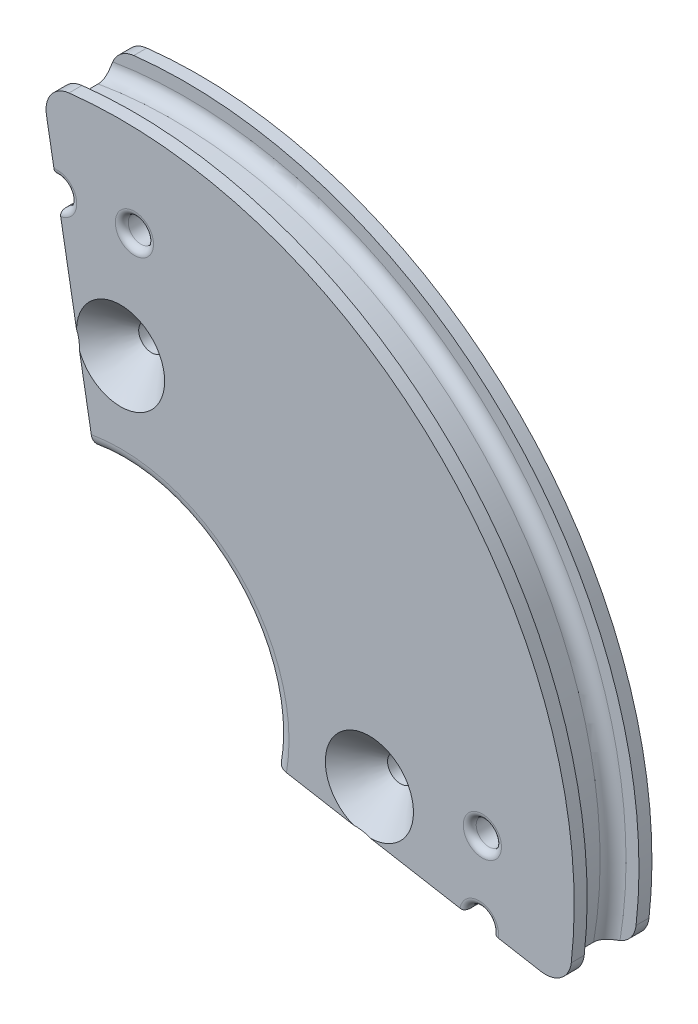
SolidWorks part; units mm, degrees
ref_plane "Front" through (0, 0, 0) normal (0, 0, 1) x (1, 0, 0)
ref_plane "Top" through (0, 0, 0) normal (0, 1, 0) x (1, 0, 0)
ref_plane "Right" through (0, 0, 0) normal (1, 0, 0) x (0, 0, -1)
sketch "Sketch1" plane through (0, 0, 0) normal (0, 0, 1) x (1, 0, 0)
  circle A2 centre (9.6, 0) radius 0.5
  circle A24 centre (0, 0) radius 17
  circle A25 centre (0, 0) radius 6
  circle A30 centre (0, -9.6) radius 0.5
  circle A32 centre (-9.6, 0) radius 0.5
  circle A34 centre (0, 9.6) radius 0.5
  point P20 (0, 0)
  dimension "D1" = 4
  dimension "D2" = 34
  dimension "D3" = 12
extrude "Boss-Extrude1" add sketch "Sketch1" along normal mid plane 3
sketch "Sketch2" plane through (0, 0, 0) normal (0, 1, 0) x (1, 0, 0)
  line L1 (0, 0) -> (0, 3.24) construction
  line L2 (17, 0) -> (19.1765, -2.75) construction
  line L3 (17, -1.5) -> (17, 1.5) construction
  line L4 (-17, 0) -> (-16.5, 0) construction
  line L5 (-17, 1.5) -> (-17, -1.5) construction
  line L6 (-16.5, -0.5) -> (-16.5, 0.5)
  line L7 (-17, 1) -> (-17, -1)
  arc A1 (-16.5, 0.5) -> (-17, 1) centre (-17, 0.5) ccw
  arc A2 (-16.5, -0.5) -> (-17, -1) centre (-17, -0.5) cw
  dimension "D1" = 33
  dimension "D2" = 2
revolve "Cut-Revolve1" cut sketch "Sketch2" angle 360 about L1
sketch "Sketch3" plane through (0, 0, 1.5) normal (0, 0, 1) x (1, 0, 0)
  line L0 (-17, 0) -> (0, 0)
  line L3 (0, 0) -> (2.952, 16.7417)
  arc A1 (-17, 0) -> (2.952, 16.7417) centre (0, 0) cw
  circle A2 centre (0, 0) radius 6 construction
  circle A3 centre (0, 0) radius 17 construction
  dimension "D4" = 100
sketch "Sketch7" plane through (0, 0, 0) normal (0, 1, 0) x (1, 0, 0)
  line L0 (1.4542, 0) -> (0, 0) construction
  line L1 (17, 1.5) -> (17.5, 1.5)
  line L2 (17, 1.5) -> (17, 1)
  line L3 (17, 1) -> (17.5, 1)
  line L4 (17.5, 1.5) -> (17.5, 1)
  line L5 (0, 0) -> (0, 3.1931) construction
  line L6 (17.5, -1.5) -> (17.5, -1)
  line L7 (17, -1) -> (17.5, -1)
  line L8 (17, -1.5) -> (17, -1)
  line L9 (17, -1.5) -> (17.5, -1.5)
  dimension "D1" = 0.5
revolve "Revolve1" add sketch "Sketch7" angle 360 about L5
sketch "Sketch4" plane through (0, 0, 0) normal (0, 0, 1) x (1, 0, 0)
  line L0 (-3.309, 18.7662) -> (0, 0)
  line L1 (0, 0) -> (12.0208, 12.0208) construction
  line L2 (0, 0) -> (-16.6927, 0) construction
  line L3 (18.7662, -3.309) -> (0, 0)
  line L5 (-3.309, 18.7662) -> (-24.9321, 18.7662)
  line L6 (-24.9321, 18.7662) -> (-24.9321, -21.7847)
  line L7 (-24.9321, -21.7847) -> (18.7662, -21.7847)
  line L10 (18.7662, -3.309) -> (18.7662, -21.7847)
  line L11 (-3.309, 18.7662) -> (18.7662, -3.309) construction
  point P0 (7.7286, 7.7286)
  dimension "D1" = 135
  dimension "D2" = 110
extrude "Cut-Extrude1" cut sketch "Sketch4" against normal through all both and the other way through all
sketch "Sketch5" plane through (0, 0, 1.5) normal (0, 0, 1) x (1, 0, 0)
  line L0 (0, 0) -> (12.3744, 12.3744) construction
  line L1 (-1.0419, 5.9088) -> (-3.0388, 17.2341) construction
  circle A0 centre (-2.4395, 13.835) radius 0.5
  circle A1 centre (0.5347, 13.9573) radius 0.4873
  arc A2 (17.2341, -3.0388) -> (-3.0388, 17.2341) centre (0, 0) ccw construction
  circle A3 centre (13.9573, 0.5347) radius 0.4873
  circle A4 centre (13.835, -2.4395) radius 0.5
  point P12 (0.5347, 13.9573)
  dimension "D1" = 1
extrude "Cut-Extrude2" cut sketch "Sketch5" against normal through all both and the other way through all
fillet "Fillet1" radius 0.5 2 edges at (4.2426, 4.2426, 1.5) (4.2426, 4.2426, -1.5)
chamfer "Chamfer1" distance 1.2 angle 45 2 edges at (10.1, 0, 1.5) (0.5, 9.6, 1.5)
sketch "Sketch6" plane through (0, 0, -1.5) normal (0, 0, -1) x (-1, 0, 0)
  line L0 (0, 0) -> (-12.3744, 12.3744) construction
  line L1 (-12.3744, 12.3744) -> (1.3226, 15.1171)
  line L2 (1.3226, 15.1171) -> (0, 0)
  line L3 (-12.3744, 12.3744) -> (-15.1171, -1.3226)
  line L4 (-15.1171, -1.3226) -> (0, 0)
  arc A1 (3.0388, 17.2341) -> (-17.2341, -3.0388) centre (0, 0) ccw construction
  dimension "D1" = 50
fillet "Fillet2" radius 1 2 edges at (17.2341, -3.0388, 1.25) (-3.0388, 17.2341, -1.25)
fillet "Fillet3" radius 0.25 12 edges at (-2.5263, 14.3274, 0) (-1.9471, 13.9218, 1.5) (-2.3527, 13.3426, 0) (-1.9471, 13.9218, -1.5) (13.3426, -2.3527, 0) (13.9218, -1.9471, 1.5) (14.3274, -2.5263, 0) (13.9218, -1.9471, -1.5) (13.47, 0.5347, -1.5) (14.4445, 0.5347, 1.5) (1.022, 13.9573, -1.5) (1.022, 13.9573, 1.5)
